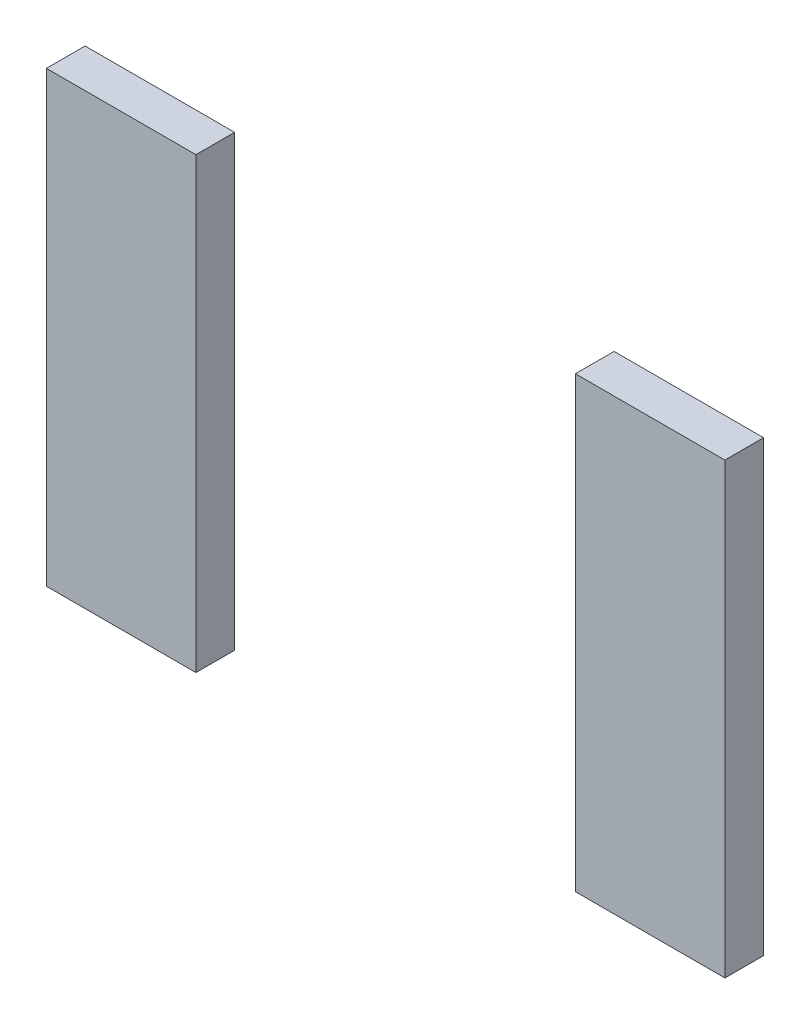
SolidWorks part; units mm, degrees
material "Polyurethane Foam Flexible"
ref_plane "Front Plane" through (0, 0, 0) normal (0, 0, 1) x (1, 0, 0)
ref_plane "Top Plane" through (0, 0, 0) normal (0, 1, 0) x (1, 0, 0)
ref_plane "Right Plane" through (0, 0, 0) normal (1, 0, 0) x (0, 0, -1)
sketch "Sketch1" plane through (0, 0, 0) normal (0, 0, 1) x (1, 0, 0)
  line L0 (35.165, 24.84) -> (35.165, -24.84) construction
  line L1 (16.115, 19.05) -> (28.815, 19.05)
  line L2 (16.115, 19.05) -> (16.115, -19.05)
  line L3 (16.115, -19.05) -> (28.815, -19.05)
  line L4 (28.815, 19.05) -> (28.815, -19.05)
  line L5 (16.115, 19.05) -> (28.815, -19.05) construction
  line L6 (16.115, -19.05) -> (28.815, 19.05) construction
  line L7 (0, 0) -> (0, 24.84) construction
  line L8 (-35.165, 24.84) -> (35.165, 24.84) construction
  line L9 (-16.115, -19.05) -> (-28.815, 19.05) construction
  line L10 (-16.115, 19.05) -> (-28.815, -19.05) construction
  line L11 (-28.815, 19.05) -> (-28.815, -19.05)
  line L12 (-16.115, -19.05) -> (-28.815, -19.05)
  line L13 (-16.115, 19.05) -> (-16.115, -19.05)
  line L14 (-16.115, 19.05) -> (-28.815, 19.05)
  point P4 (22.465, 0)
  point P17 (-22.465, 0)
  dimension "D1" = 12.7
  dimension "D2" = 38.1
  dimension "D3" = 6.35
extrude "Boss-Extrude1" add sketch "Sketch1" along normal blind 3.2868
